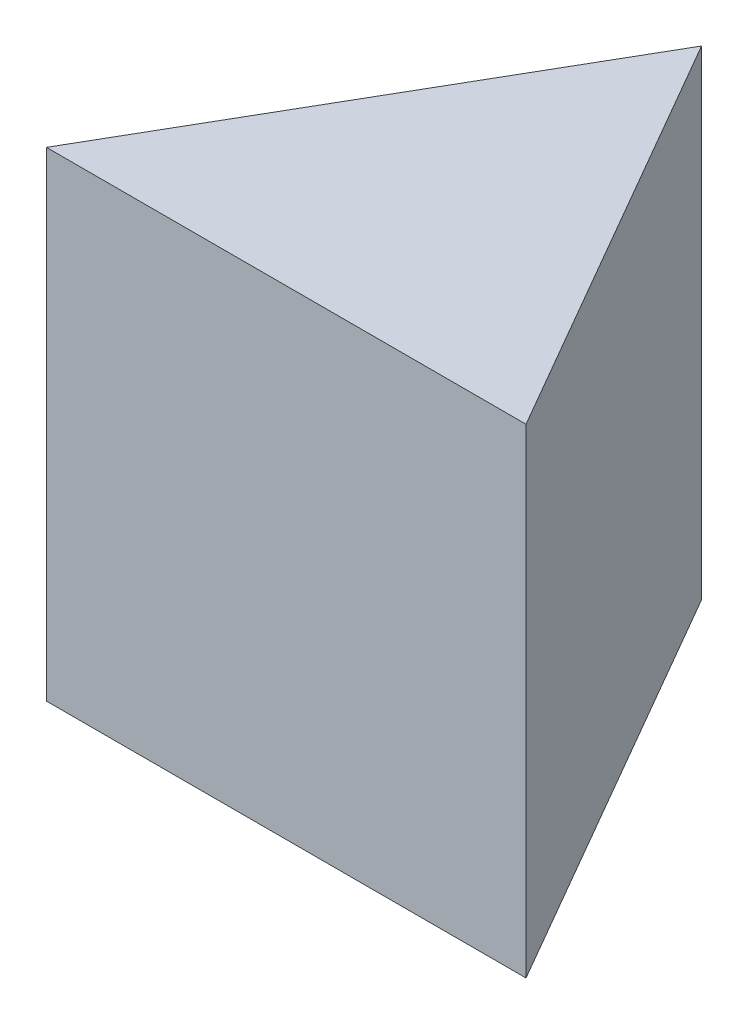
SolidWorks part; units mm, degrees
ref_plane "Front Plane" through (0, 0, 0) normal (0, 0, 1) x (1, 0, 0)
ref_plane "Top Plane" through (0, 0, 0) normal (0, 1, 0) x (1, 0, 0)
ref_plane "Right Plane" through (0, 0, 0) normal (1, 0, 0) x (0, 0, -1)
sketch "Sketch1" plane through (0, 0, 0) normal (0, 1, 0) x (1, 0, 0)
  line L0 (-5, 7.8776) -> (-10, -0.7826)
  line L1 (-5, 7.8776) -> (0, -0.7826)
  line L2 (-10, -0.7826) -> (0, -0.7826)
  dimension "D1" = 10
  dimension "D2" = 60
  dimension "D3" = 60
extrude "Boss-Extrude1" add sketch "Sketch1" along normal blind 10 contours L1 L2 L0
